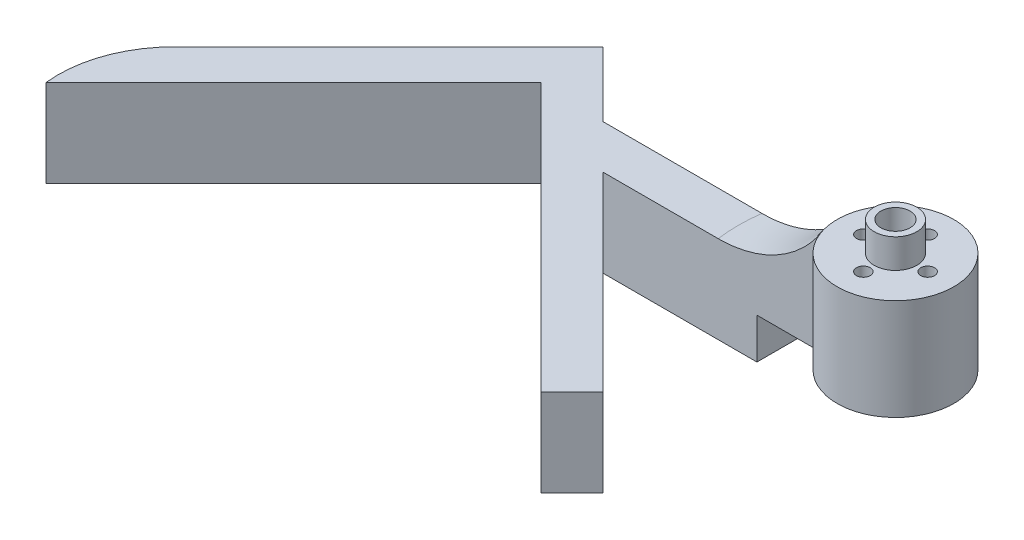
SolidWorks part; units mm, degrees
ref_plane "Front Plane" through (0, 0, 0) normal (0, 0, 1) x (1, 0, 0)
ref_plane "Top Plane" through (0, 0, 0) normal (0, 1, 0) x (1, 0, 0)
ref_plane "Right Plane" through (0, 0, 0) normal (1, 0, 0) x (0, 0, -1)
sketch "Sketch1" plane through (0, 0, 0) normal (0, 1, 0) x (1, 0, 0)
  circle A3 centre (0, -38.254) radius 38.254 construction
  circle A4 centre (0, -40.254) radius 40.254 construction
  circle A5 centre (0, -45.254) radius 45.254 construction
  dimension "D1" = 90.508
  dimension "D2" = 80.508
  dimension "D3" = 76.508
sketch "Sketch3" plane through (0, 0, 0) normal (0, 1, 0) x (1, 0, 0)
  line L8 (58.3717, -39.6268) -> (0, 18.7448)
  line L9 (0, 18.7448) -> (-58.3717, -39.6268)
  line L10 (-58.3717, -39.6268) -> (58.3717, -39.6268) construction
  line L17 (65.1069, -32.8917) -> (23.6201, 8.5951)
  line L18 (0, 32.2152) -> (-65.1069, -32.8917)
  line L19 (-65.1069, -32.8917) -> (-58.3717, -39.6268)
  line L20 (65.1069, -32.8917) -> (58.3717, -39.6268)
  line L23 (82.55, 18.1201) -> (82.55, 8.5951)
  line L26 (65.1069, -32.8917) -> (0, 32.2152) construction
  line L27 (0, 32.2152) -> (-65.1069, -32.8917) construction
  line L28 (14.0951, 18.1201) -> (82.55, 18.1201)
  line L29 (82.55, 8.5951) -> (23.6201, 8.5951)
  line L30 (14.0951, 18.1201) -> (0, 32.2152)
  circle A3 centre (0, -45.254) radius 45.254 construction
  point P13 (82.55, 13.3576)
  dimension "D1" = 45
  dimension "D2" = 45
  dimension "D3" = 82.55
  dimension "D5" = 9.525
  dimension "D7" = 82.55
  dimension "D6" = 52.9844
  dimension "D4" = 9.525
extrude "Boss-Extrude1" add sketch "Sketch3" along normal blind 19.05
sketch "Sketch11" plane through (0, 0, 0) normal (0, 1, 0) x (1, 0, 0)
  line L0 (82.55, 8.5951) -> (82.55, 18.1201) construction
  circle A0 centre (82.55, 13.3576) radius 12.7
  dimension "D1" = 25.4
extrude "Boss-Extrude2" add sketch "Sketch11" along normal blind 30.861
sketch "Sketch14" plane through (0, 0, 0) normal (0, -1, 0) x (1, 0, 0)
  circle A0 centre (89.55, -13.3576) radius 1.077
  circle A2 centre (82.55, -20.3576) radius 1.077
  circle A3 centre (75.55, -13.3576) radius 1.077
  circle A4 centre (82.55, -6.3576) radius 1.077
  circle A5 centre (82.55, -13.3576) radius 12.7 construction
  point P17 (82.55, -13.3576)
  dimension "D2" = 2.154
  dimension "D1" = 7
  dimension "D3" = 4
extrude "Cut-Extrude4" cut sketch "Sketch14" against normal through all
sketch "Sketch16" plane through (0, 0, 0) normal (0, -1, 0) x (1, 0, 0)
  line L2 (57.15, -8.5951) -> (57.15, -18.1201)
  line L7 (-65.1069, 32.8917) -> (0, -32.2152)
  line L8 (65.1069, 32.8917) -> (58.3717, 39.6268)
  line L9 (58.3717, 39.6268) -> (0, -18.7448)
  line L10 (0, -18.7448) -> (-58.3717, 39.6268)
  line L20 (-58.3717, 39.6268) -> (-65.1069, 32.8917)
  line L24 (14.0951, -18.1201) -> (70.7768, -18.1201)
  line L30 (23.6201, -8.5951) -> (65.1069, 32.8917)
  line L35 (57.15, -18.1201) -> (70.7768, -18.1201)
  line L37 (70.7768, -8.5951) -> (23.6201, -8.5951)
  line L38 (70.7768, -8.5951) -> (57.15, -8.5951)
  line L40 (0, -32.2152) -> (14.0951, -18.1201)
  arc A1 (70.7768, -18.1201) -> (70.7768, -8.5951) centre (82.55, -13.3576) ccw
  arc A3 (70.7768, -18.1201) -> (70.7768, -8.5951) centre (82.55, -13.3576) ccw
  dimension "D2" = 25.4
  dimension "D1" = 0
extrude "Cut-Extrude7" cut sketch "Sketch16" against normal blind 8.842
sketch "Sketch17" plane through (0, 19.05, 0) normal (0, 1, 0) x (1, 0, 0)
  line L0 (-65.1069, -32.8917) -> (-60.6167, -28.4015)
  line L1 (0, 32.2152) -> (-65.1069, -32.8917) construction
  line L2 (-60.6167, -28.4015) -> (-53.8815, -35.1367)
  line L3 (-58.3717, -39.6268) -> (0, 18.7448) construction
  line L4 (-53.8815, -35.1367) -> (-58.3717, -39.6268)
  line L5 (-58.3717, -39.6268) -> (-65.1069, -32.8917)
  dimension "D1" = 6.35
extrude "Cut-Extrude8" cut sketch "Sketch17" against normal through all
fillet "Fillet9" radius 25.4 1 edges at (69.85, 19.05, -13.3576)
fillet "Fillet10" radius 25.4 1 edges at (-60.6167, 9.525, 28.4015)
sketch "Sketch18" plane through (0, 30.861, 0) normal (0, 1, 0) x (1, 0, 0)
  circle A0 centre (82.55, 13.3576) radius 3.175
  dimension "D1" = 6.35
extrude "Cut-Extrude9" cut sketch "Sketch18" against normal through all
sketch "Sketch19" plane through (0, 30.861, 0) normal (0, 1, 0) x (1, 0, 0)
  circle A0 centre (82.55, 13.3576) radius 3.175
  circle A1 centre (82.55, 13.3576) radius 4.6355
  dimension "D1" = 9.271
extrude "Boss-Extrude3" add sketch "Sketch19" along normal blind 6.35
sketch "Sketch15" plane through (0, 30.861, 0) normal (0, -1, 0) x (-1, 0, 0)
  circle A0 centre (-89.55, 13.3576) radius 1.5
  circle A1 centre (-82.55, 6.3576) radius 1.5
  circle A2 centre (-75.55, 13.3576) radius 1.5
  circle A3 centre (-82.55, 20.3576) radius 1.5
  dimension "D1" = 3
extrude "Cut-Extrude6" cut sketch "Sketch15" along normal offset from surface 15 and the other way through all up to face at (82.55, 8.842, -16.5326)
equation "\"tightTol\"= 0.005in"
equation "\"normTol\"= 0.01in"
equation "\"looseTol\"= 0.02in"
equation "\"D1@Sketch1\"=\"looseTol\"+9cm"
equation "\"D2@Sketch1\"=8cm+\"looseTol\""
equation "\"D3@Sketch1\"=7.6cm+\"looseTol\""
equation "\"D2\"= 0.875 - 10.7mm"
equation "\"D1\"= 10.7mm"
equation "\"D1@Boss-Extrude1\"=40mm"
equation "\"D2@Sketch14\"= 1.9mm + \"normTol\""
equation "\"D1@Sketch15\"=3mm"
equation "\"D1@Sketch14\"=7mm"
equation "\"D19@Boss-Extrude2\"=0.250000-1.5*\"normTol\""
equation "\"D1@Cut-Extrude6\"=15mm"
equation "\"D1@Boss-Extrude2\" = 1.25 - \"looseTol\" - 1.5 * \"normTol\""
equation "\"D1@Cut-Extrude7\" = 15.7mm - 0.25 - \"looseTol\""
equation "\"D6@Sketch3\"=4.95-2.864"
equation "\"D1@Sketch19\"=0.375000in-\"normTol\""
